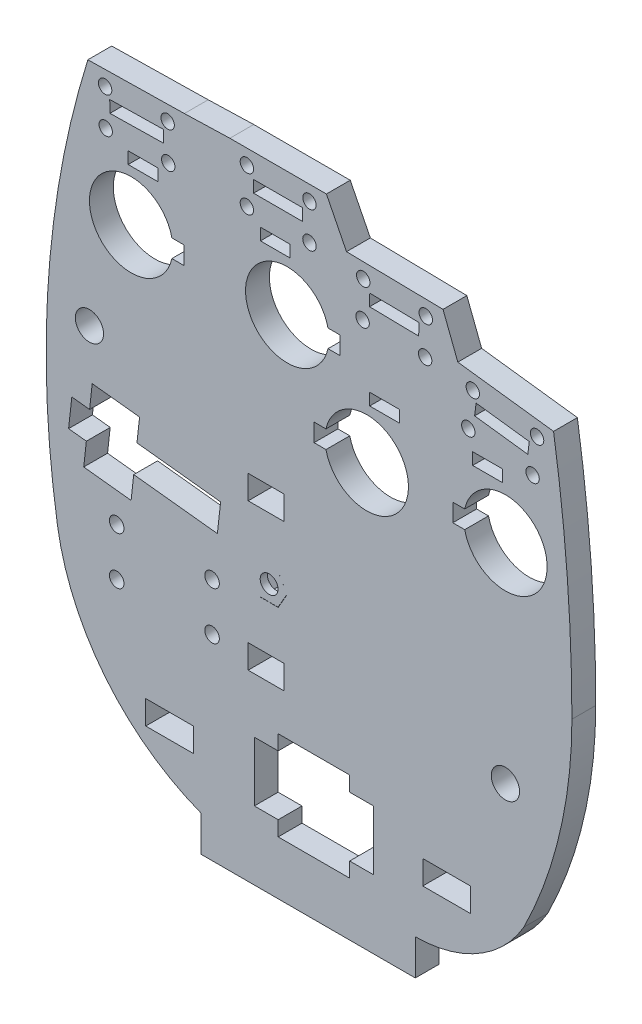
SolidWorks part; units mm, degrees
ref_plane "Front Plane" through (0, 0, 0) normal (0, 0, 1) x (1, 0, 0)
ref_plane "Top Plane" through (0, 0, 0) normal (0, 1, 0) x (1, 0, 0)
ref_plane "Right Plane" through (0, 0, 0) normal (1, 0, 0) x (0, 0, -1)
sketch "Sketch1" plane through (0, 0, 0) normal (0, 0, 1) x (1, 0, 0)
  line L0 (-4.125, 78.51) -> (-4.125, 76.51)
  line L1 (4.125, 78.51) -> (-4.125, 78.51)
  line L2 (-12.9786, -18) -> (-12.9786, -24)
  line L3 (-10.203, 23.9877) -> (-9.6615, 28.8655)
  line L4 (-4.125, 76.51) -> (4.125, 76.51)
  line L5 (4.125, 76.51) -> (4.125, 78.51)
  line L6 (-35.1781, 26.7603) -> (-34.6366, 31.6381)
  line L7 (10.3588, 63.1512) -> (10.3588, 60.1512)
  line L8 (-8.1, 82.51) -> (8.1, 82.51)
  line L9 (8.3588, 63.1512) -> (10.3588, 63.1512)
  line L10 (11.4712, 75.8064) -> (27.6688, 75.5236)
  line L11 (32.6473, 57.3216) -> (37.6473, 57.3216)
  line L12 (0, 0) -> (-23.845, 0) construction
  line L13 (10.3588, 60.1512) -> (8.3588, 60.1512)
  line L14 (-17.8416, 63.1512) -> (-15.8416, 63.1512)
  line L15 (-15.8416, 63.1512) -> (-15.8416, 60.1512)
  line L16 (-15.8416, 60.1512) -> (-17.8416, 60.1512)
  line L17 (32.6473, 55.3216) -> (37.6473, 55.3216)
  line L18 (37.6473, 55.3216) -> (37.6473, 57.3216)
  line L19 (32.6473, 57.3216) -> (32.6473, 55.3216)
  line L20 (-28.2745, 78.062) -> (-19.2758, 78.2192)
  line L21 (-28.2745, 78.062) -> (-28.2395, 76.0623)
  line L22 (-10.0543, 52.8756) -> (-18.0543, 52.8756) construction
  line L23 (-9.6615, 28.8655) -> (-23.7037, 30.4244)
  line L24 (-28.2395, 76.0623) -> (-19.2408, 76.2195)
  line L25 (-24.6866, 21.571) -> (-32.6377, 22.4537)
  line L26 (-32.6377, 22.4537) -> (-32.1964, 26.4293)
  line L27 (-24.2452, 25.5466) -> (-10.203, 23.9877)
  line L28 (-19.2408, 76.2195) -> (-19.2758, 78.2192)
  line L29 (15.3631, 57.3216) -> (20.3631, 57.3216)
  line L30 (15.3631, 55.3216) -> (20.3631, 55.3216)
  line L31 (-12.9786, -24) -> (23.0214, -24)
  line L32 (20.3631, 55.3216) -> (20.3631, 57.3216)
  line L33 (23.0214, -24) -> (23.0214, -18)
  line L34 (15.3631, 57.3216) -> (15.3631, 55.3216)
  line L35 (-2.9786, 72.1512) -> (2.0214, 72.1512)
  line L36 (15.3758, 71.7376) -> (15.3409, 69.7379)
  line L37 (15.3409, 69.7379) -> (23.5897, 69.5939)
  line L38 (8.0257, 48.3216) -> (6.0257, 48.3216)
  line L39 (-2.9786, 70.1512) -> (2.0214, 70.1512)
  line L40 (23.6246, 71.5936) -> (15.3758, 71.7376)
  line L41 (6.0257, 48.3216) -> (6.0257, 45.3216)
  line L42 (23.5897, 69.5939) -> (23.6246, 71.5936)
  line L43 (-23.845, 0) -> (-23.845, 82.14) construction
  line L44 (2.0214, 70.1512) -> (2.0214, 72.1512)
  line L45 (19.57, 75.665) -> (19.6234, 78.7251) construction
  line L46 (-2.9786, 72.1512) -> (-2.9786, 70.1512)
  line L47 (42.1536, 63.5476) -> (33.2239, 64.6755)
  line L48 (6.0257, 45.3216) -> (8.0257, 45.3216)
  line L49 (29.3099, 45.3216) -> (31.3099, 45.3216)
  line L50 (29.3099, 48.3216) -> (29.3099, 45.3216)
  line L51 (31.3099, 48.3216) -> (29.3099, 48.3216)
  line L52 (-23.2624, 34.3999) -> (-31.2135, 35.2826)
  line L53 (33.2239, 64.6755) -> (32.9732, 62.6912)
  line L54 (-25.179, 72.1512) -> (-20.179, 72.1512)
  line L55 (-31.9438, 81.9985) -> (-15.7462, 82.2815)
  line L56 (46.2262, 67.065) -> (30.1538, 69.095)
  line L57 (-25.179, 70.1512) -> (-20.179, 70.1512)
  line L58 (32.9732, 62.6912) -> (41.903, 61.5633)
  line L59 (-20.179, 70.1512) -> (-20.179, 72.1512)
  line L60 (-25.179, 72.1512) -> (-25.179, 70.1512)
  line L61 (41.903, 61.5633) -> (42.1536, 63.5476)
  line L62 (-35.1781, 26.7603) -> (-32.1964, 26.4293)
  line L63 (-4, -2.5) -> (0, -2.5)
  line L64 (12, 0) -> (0, 0)
  line L65 (12, 0) -> (12, -2.5)
  line L66 (12, -15) -> (0, -15)
  line L67 (-31.2135, 35.2826) -> (-31.6549, 31.3071)
  line L68 (-23.7037, 30.4244) -> (-23.2624, 34.3999)
  line L69 (-34.6366, 31.6381) -> (-31.6549, 31.3071)
  line L70 (-24.6866, 21.571) -> (-24.2452, 25.5466)
  line L71 (16, -7.5) -> (41.235, -7.5) construction
  line L72 (0, -15) -> (0, -12.5)
  line L73 (-4, -12.5) -> (-4, -2.5)
  line L74 (-4, -12.5) -> (0, -12.5)
  line L75 (0, -2.5) -> (0, 0)
  line L76 (0, 0) -> (0, 82.51) construction
  line L77 (-22.0543, 52.8756) -> (-27.0543, 52.8756) construction
  line L78 (-10.0543, -2.1244) -> (-18.0543, -2.1244) construction
  line L79 (-22.0543, -2.1244) -> (-27.0543, -2.1244) construction
  line L80 (0, 0) -> (19.57, 0) construction
  line L81 (16, -12.5) -> (12, -12.5)
  line L82 (16, -12.5) -> (16, -2.5)
  line L83 (16, -2.5) -> (12, -2.5)
  line L84 (12, -12.5) -> (12, -15)
  line L85 (-9.9323, 26.4266) -> (5.8267, 24.6771) construction
  line L86 (0, 23.5609) -> (-3, 23.5609)
  line L87 (-3, 23.5609) -> (-4.5, 20.9629)
  line L88 (-4.5, 20.9629) -> (-3, 18.3648)
  line L89 (19.57, 0) -> (19.57, 75.665) construction
  line L90 (0, 0) -> (38.19, 0) construction
  line L91 (38.19, 0) -> (38.19, 68.08) construction
  line L92 (30.1538, 69.095) -> (27.6688, 75.5236)
  line L93 (11.4712, 75.8064) -> (8.1, 82.51)
  line L94 (-8.1, 82.51) -> (-15.7462, 82.2815)
  line L95 (-35.1781, 26.7603) -> (49.3063, 26.7603) construction
  line L96 (37.6888, 64.1115) -> (38.19, 68.08) construction
  line L97 (-3, 18.3648) -> (0, 18.3648)
  line L98 (0, 18.3648) -> (1.5, 20.9629)
  line L99 (1.5, 20.9629) -> (0, 23.5609)
  line L100 (0, 18.3648) -> (-3, 23.5609) construction
  line L101 (0, 23.5609) -> (-3, 18.3648) construction
  line L102 (38.1473, 11.8216) -> (-37.0527, 11.8216) construction
  line L103 (-29.0506, 79.5486) -> (-31.9001, 79.4989) construction
  line L104 (0.9634, 10.717) -> (0.9634, 6.717)
  line L105 (0.9634, 6.717) -> (-5.0366, 6.717)
  line L106 (-5.0366, 6.717) -> (-5.0366, 10.717)
  line L107 (-5.0366, 10.717) -> (0.9634, 10.717)
  line L108 (-5.0366, 31.3356) -> (0.9634, 31.3356)
  line L109 (-5.0366, 35.3356) -> (-5.0366, 31.3356)
  line L110 (0.9634, 35.3356) -> (-5.0366, 35.3356)
  line L111 (0.9634, 31.3356) -> (0.9634, 35.3356)
  line L112 (-31.9001, 79.4989) -> (-31.9438, 81.9985) construction
  line L113 (-18.5521, 79.732) -> (-15.7025, 79.7819) construction
  line L114 (-15.7025, 79.7819) -> (-15.7462, 82.2815) construction
  line L115 (-23.7751, 78.1406) -> (-23.845, 82.14) construction
  line L116 (5.25, 80.01) -> (8.1, 80.01) construction
  line L117 (8.1, 80.01) -> (8.1, 82.51) construction
  line L118 (-5.25, 80.01) -> (-8.1, 80.01) construction
  line L119 (-22.0543, 0.2506) -> (-27.0543, 0.2506) construction
  line L120 (-8.1, 80.01) -> (-8.1, 82.51) construction
  line L121 (-10.0543, 1.8756) -> (-10.0543, -2.1244) construction
  line L122 (32.6681, 66.2576) -> (29.8406, 66.6147) construction
  line L123 (-10.0543, 52.8756) -> (-10.0543, 46.8756) construction
  line L124 (-10.0543, 1.8756) -> (-18.0543, 1.8756) construction
  line L125 (-18.0543, 1.8756) -> (-18.0543, -2.1244) construction
  line L126 (29.8406, 66.6147) -> (30.1538, 69.095) construction
  line L127 (14.2772, 73.257) -> (11.4276, 73.3067) construction
  line L128 (-22.0543, 0.2506) -> (-22.0543, -2.1244) construction
  line L129 (-27.0543, 0.2506) -> (-27.0543, -2.1244) construction
  line L130 (32.6681, 66.2576) -> (31.9162, 60.3049) construction
  line L131 (-10.0543, 46.8756) -> (-18.0543, 46.8756) construction
  line L132 (-27.0543, 52.8756) -> (-27.0543, 50.5006) construction
  line L133 (-18.0543, 46.8756) -> (-18.0543, 52.8756) construction
  line L134 (11.4712, 75.8064) -> (11.4276, 73.3067) construction
  line L135 (-22.0543, 6.717) -> (-22.0543, 10.717) construction
  line L136 (-22.0543, 10.717) -> (-27.0543, 10.717) construction
  line L137 (-27.0543, 50.5006) -> (-22.0543, 50.5006) construction
  line L138 (-22.0543, 52.8756) -> (-22.0543, 50.5006) construction
  line L139 (-27.0543, 10.717) -> (-27.0543, 6.717) construction
  line L140 (-27.0543, 6.717) -> (-22.0543, 6.717) construction
  line L141 (-27.0543, 38.7272) -> (-22.0543, 38.7272) construction
  line L142 (-22.0543, 38.7272) -> (-22.0543, 42.7272) construction
  line L143 (-22.0543, 42.7272) -> (-27.0543, 42.7272) construction
  line L144 (-27.0543, 42.7272) -> (-27.0543, 38.7272) construction
  line L145 (24.7756, 73.0738) -> (27.6251, 73.024) construction
  line L146 (27.6251, 73.024) -> (27.6688, 75.5236) construction
  line L147 (43.4577, 64.8948) -> (46.2853, 64.5376) construction
  line L148 (43.4577, 64.8948) -> (42.7059, 58.9421) construction
  line L149 (42.7059, 58.9421) -> (45.5334, 58.5849) construction
  line L150 (45.5334, 58.5849) -> (46.2853, 64.5376) construction
  line L151 (24.7756, 73.0738) -> (24.6709, 67.0747) construction
  line L152 (14.2772, 73.257) -> (14.1725, 67.2579) construction
  line L153 (-18.5521, 79.732) -> (-18.4473, 73.733) construction
  line L154 (-29.0506, 79.5486) -> (-28.9458, 73.5496) construction
  line L155 (38.1473, 46.8216) -> (38.1473, 11.8216) construction
  line L156 (-31.6, 35.8756) -> (-31.6, -2.1244) construction
  line L157 (-31.6, -2.1244) -> (-6.6, -2.1244) construction
  line L158 (-6.6, -2.1244) -> (-6.6, 35.8756) construction
  line L159 (-6.6, 35.8756) -> (-31.6, 35.8756) construction
  arc A0 (-37.0527, 11.8216) -> (-31.9438, 81.9985) centre (115.9422, 35.958) cw
  circle A1 centre (-1.5, 20.9629) radius 4.5 construction
  arc A2 (8.3588, 63.1512) -> (8.3588, 60.1512) centre (1.5214, 61.6512) ccw
  arc A3 (8.0257, 45.3216) -> (8.0257, 48.3216) centre (14.8631, 46.8216) ccw
  arc A4 (-17.8416, 63.1512) -> (-17.8416, 60.1512) centre (-24.679, 61.6512) ccw
  arc A5 (31.3099, 45.3216) -> (31.3099, 48.3216) centre (38.1473, 46.8216) ccw
  arc A6 (23.0214, -18) -> (41.235, -7.5) centre (23.0214, 3.0469) ccw
  arc A7 (49.3063, 26.7603) -> (41.235, -7.5) centre (-27.4409, 26.7603) cw
  arc A8 (-37.0527, 11.8216) -> (-12.9786, -18) centre (0.8651, 17.8035) ccw
  arc A9 (49.3063, 26.7603) -> (46.2262, 67.065) centre (-215.9296, 26.7603) ccw
  circle A10 centre (-27.1, 24.8756) radius 1.225 construction
  circle A11 centre (38.1473, 11.8216) radius 2.375
  circle A12 centre (-14, -9.1244) radius 2.375 construction
  circle A13 centre (-27.1, 8.8756) radius 1.225
  circle A14 centre (-27.1, 16.8756) radius 1.225
  circle A15 centre (-11.1, 8.8756) radius 1.225
  circle A16 centre (-11.1, 16.8756) radius 1.225
  circle A17 centre (-11.1, 24.8756) radius 1.225 construction
  circle A18 centre (-5.25, 80.01) radius 1.125
  circle A19 centre (32.6681, 66.2576) radius 1.125
  circle A22 centre (-31.6815, 43.4564) radius 2.375
  circle A49 centre (5.25, 80.01) radius 1.125
  circle A50 centre (5.25, 74.01) radius 1.125
  circle A51 centre (-5.25, 74.01) radius 1.125
  circle A52 centre (-29.0506, 79.5486) radius 1.125
  circle A53 centre (-18.5521, 79.732) radius 1.125
  circle A54 centre (-28.9458, 73.5496) radius 1.125
  circle A55 centre (-18.4473, 73.733) radius 1.125
  circle A56 centre (24.6709, 67.0747) radius 1.125
  circle A57 centre (14.1725, 67.2579) radius 1.125
  circle A58 centre (24.7756, 73.0738) radius 1.125
  circle A59 centre (14.2772, 73.257) radius 1.125
  circle A60 centre (31.9162, 60.3049) radius 1.125
  circle A61 centre (43.4577, 64.8948) radius 1.125
  circle A63 centre (42.7059, 58.9421) radius 1.125
  dimension "D1" = 4.75
  dimension "D2" = 2.25
  dimension "D5" = 7
  dimension "D45" = 9
  dimension "D89" = 2.45
  dimension "D10" = 0.9634
  dimension "D11" = 1.5214
  dimension "D12" = 2.0214
  dimension "D16" = 6.0257
  dimension "D18" = 8.3588
  dimension "D26" = 15.3631
  dimension "D30" = 20.3631
  dimension "D33" = 23.0214
  dimension "D38" = 29.3099
  dimension "D42" = 32.6473
  dimension "D49" = 5.0366
  dimension "D50" = 9.6615
  dimension "D51" = 10.203
  dimension "D52" = 10.0543
  dimension "D53" = 12.9786
  dimension "D54" = 14
  dimension "D56" = 15.8416
  dimension "D59" = 18.0543
  dimension "D62" = 20.179
  dimension "D63" = 22.0543
  dimension "D68" = 31.6815
  dimension "D71" = 1.8756
  dimension "D72" = 6.717
  dimension "D76" = 21.571
  dimension "D77" = 31.3356
  dimension "D79" = 43.4564
  dimension "D80" = 45.3216
  dimension "D81" = 46.8756
  dimension "D82" = 55.3216
  dimension "D84" = 60.1512
  dimension "D86" = 70.1512
  dimension "D93" = 9.1244
  dimension "D14" = 82.51
  dimension "D19" = 23.845
  dimension "D21" = 82.14
  dimension "D22" = 4
  dimension "D23" = 19.57
  dimension "D24" = 75.665
  dimension "D31" = 38.19
  dimension "D32" = 68.08
  dimension "D35" = 4
  dimension "D36" = 16.2
  dimension "D37" = 2
  dimension "D40" = 46.8216
  dimension "D41" = 14.8631
  dimension "D44" = 24.679
  dimension "D15" = 3
  dimension "D28" = 0
  dimension "D46" = 0.7292
  dimension "D47" = 4.9078
  dimension "D48" = 25.1285
  dimension "D55" = 24
  dimension "D20" = 10
  dimension "D25" = 12
  dimension "D27" = 2.5
  dimension "D57" = 4
  dimension "D66" = 2.85
  dimension "D67" = 2.5
  dimension "D78" = 6
  dimension "D13" = 4
  dimension "D43" = 2.85
  dimension "D58" = 2.5
  dimension "D65" = 2.85
  dimension "D39" = 2.85
  dimension "D70" = 2.5
  dimension "D17" = 4
  dimension "D73" = 9.0001
  dimension "D74" = 9.0007
  dimension "D29" = 2.5
  dimension "D34" = 6
  dimension "D61" = 6
  dimension "D60" = 8.1
  dimension "D69" = 6
  dimension "D83" = 8.1
  dimension "D75" = 35
  dimension "D85" = 2
  dimension "D87" = 38
  dimension "D88" = 25
  dimension "D90" = 6.6
  dimension "D91" = 2.1244
  dimension "D92" = 8
  dimension "D95" = 8
  dimension "D96" = 4.5
  dimension "D94" = 16
  dimension "D97" = 2
extrude "Boss-Extrude1" add sketch "Sketch1" along normal blind 4
sketch "Sketch3" plane through (0, 0, 0) normal (0, 0, -1) x (-1, 0, 0)
  line L1 (-24.2714, -10) -> (-32.2714, -10)
  line L2 (-32.2714, -10) -> (-32.2714, -6)
  line L3 (-32.2714, -6) -> (-24.2714, -6)
  line L4 (-24.2714, -6) -> (-24.2714, -10)
  line L5 (-5.0214, -24) -> (-5.0214, -4.0378) construction
  line L6 (12.9786, -24) -> (-23.0214, -24) construction
  line L7 (14.2286, -6) -> (14.2286, -10)
  line L8 (22.2286, -6) -> (14.2286, -6)
  line L9 (22.2286, -10) -> (22.2286, -6)
  line L10 (14.2286, -10) -> (22.2286, -10)
  dimension "D1" = 4
  dimension "D2" = 8
  dimension "D3" = 14
  dimension "D4" = 19.25
extrude "Cut-Extrude2" cut sketch "Sketch3" against normal through all
sketch "Sketch4" plane through (0, 0, 0) normal (0, 0, -1) x (-1, 0, 0)
  line L0 (19.1, 16.8756) -> (19.1, 8.8756) construction
  circle A0 centre (27.1, 16.8756) radius 2.1
  circle A1 centre (27.1, 8.8756) radius 2.1
  circle A2 centre (11.1, 8.8756) radius 2.1
  circle A3 centre (11.1, 16.8756) radius 2.1
  dimension "D1" = 4.2
extrude "Cut-Extrude3" cut sketch "Sketch4" against normal blind 2
sketch "Sketch2" plane through (0, 0, 4) normal (0, 0, 1) x (1, 0, 0)
  line L1 (-19.1, 16.8756) -> (-19.1, 8.8756) construction
  circle A0 centre (-11.1, 16.8756) radius 2.1
  circle A1 centre (-11.1, 8.8756) radius 2.1
  circle A2 centre (-27.1, 8.8756) radius 2.1
  circle A3 centre (-27.1, 16.8756) radius 2.1
  dimension "D1" = 4.2
  dimension "D2" = 27.1
extrude "Cut-Extrude1" [suppressed] cut sketch "Sketch2" against normal blind 2
sketch "Sketch5" plane through (0, 0, 4) normal (0, 0, 1) x (1, 0, 0)
  line L0 (-10.203, 24.0723) -> (-9.6615, 28.8655) construction
  line L1 (-3.0188, 18.3917) -> (-0.0188, 18.3917)
  line L2 (-0.0188, 18.3917) -> (1.4812, 20.9898)
  line L3 (1.4812, 20.9898) -> (-0.0188, 23.5878)
  line L4 (-0.0188, 23.5878) -> (-3.0188, 23.5878)
  line L5 (-3.0188, 23.5878) -> (-4.5188, 20.9898)
  line L6 (-4.5188, 20.9898) -> (-3.0188, 18.3917)
  line L7 (-9.9323, 26.4689) -> (6.8213, 24.5762) construction
  line L9 (-35.1872, 26.7613) -> (-34.6457, 31.6391) construction
  line L10 (-23.2609, 34.4137) -> (-23.7037, 30.4244) construction
  line L11 (-24.685, 21.585) -> (-32.6362, 22.4677) construction
  line L12 (-32.6362, 22.4677) -> (-32.1964, 26.4293) construction
  line L13 (-24.2452, 25.5466) -> (-9.6818, 23.9298) construction
  line L14 (-23.2609, 34.4137) -> (-31.212, 35.2964) construction
  line L15 (-35.1872, 26.7613) -> (-32.1964, 26.4293) construction
  line L16 (-23.7037, 30.4244) -> (-9.6615, 28.8655) construction
  line L17 (-24.685, 21.585) -> (-24.2452, 25.5466) construction
  line L18 (-34.6457, 31.6391) -> (-31.6549, 31.3071) construction
  line L19 (-31.6549, 31.3071) -> (-31.212, 35.2964) construction
  line L20 (-9.6615, 28.8655) -> (-23.7037, 30.4244) construction
  circle A0 centre (-1.5188, 20.9898) radius 4.5 construction
  circle A1 centre (-1.5188, 20.9898) radius 1.5
  dimension "D3" = 3
  dimension "D6" = 9
  dimension "D1" = 2.5981
  dimension "D2" = 1.5
  dimension "D4" = 9.6615
  dimension "D5" = 10.203
  dimension "D7" = 4.9078
  dimension "D8" = 25.1285
  dimension "D9" = 24.0723
extrude "Boss-Extrude2" add sketch "Sketch5" against normal blind 1.2
equation "\"D14@Sketch1\"= \"HL@parametersSketch@prostheticParameters.SLDPRT\" * 0.446'Mioddle Base Frame "
equation "\"D19@Sketch1\"= \"HB@parametersSketch@prostheticParameters.SLDPRT\" * 0.251'Index Base Frame X"
equation "\"D21@Sketch1\"= \"HL@parametersSketch@prostheticParameters.SLDPRT\" * 0.444'Index Base Frame Y"
equation "\"D23@Sketch1\"= \"HB@parametersSketch@prostheticParameters.SLDPRT\" * 0.206'Ring Base Frame X"
equation "\"D24@Sketch1\"= \"HL@parametersSketch@prostheticParameters.SLDPRT\" * 0.409'Ring Base Frame Y"
equation "\"D31@Sketch1\"= \"HB@parametersSketch@prostheticParameters.SLDPRT\" * 0.402'Pinky Base Frame X"
equation "\"D32@Sketch1\"= \"HL@parametersSketch@prostheticParameters.SLDPRT\" * 0.368'Pinky Base Frame Y"
equation "\"D36@Sketch1\"= \"fingerWidth@parametersSketch@prostheticParameters.SLDPRT\"'Fingers Width"
equation "\"D76@Sketch1\"= \"HL@parametersSketch@prostheticParameters.SLDPRT\" * 0.1166'Hole Thumb Y"
equation "\"D51@Sketch1\"= \"HB@parametersSketch@prostheticParameters.SLDPRT\" * 0.1074'Hole Thumb X1"
equation "\"D50@Sketch1\" = \"HB@parametersSketch@prostheticParameters.SLDPRT\" * 0.1017'Hole Thumb X2"
equation "\"D73@Sketch1\"=(\"fingerWidth@parametersSketch@prostheticParameters.SLDPRT\" * 0.55556)"
equation "\"D74@Sketch1\"=(\"fingerWidth@parametersSketch@prostheticParameters.SLDPRT\" * 0.5556)"
equation "\"D60@Sketch1\"= \"fingerWidth@parametersSketch@prostheticParameters.SLDPRT\" / 2"
equation "\"D83@Sketch1\"= \"fingerWidth@parametersSketch@prostheticParameters.SLDPRT\" / 2"
equation "\"D1@Sketch1\"= 4.45 + \"tol1@parametersSketch@prostheticParameters.SLDPRT\""
equation "\"D2@Sketch1\"= 1.95 + \"tol1@parametersSketch@prostheticParameters.SLDPRT\""
equation "\"D4@Sketch5\"= \"D50@Sketch1\"'Support nut"
equation "\"D5@Sketch5\"= \"D51@Sketch1\"'Support Nut"
